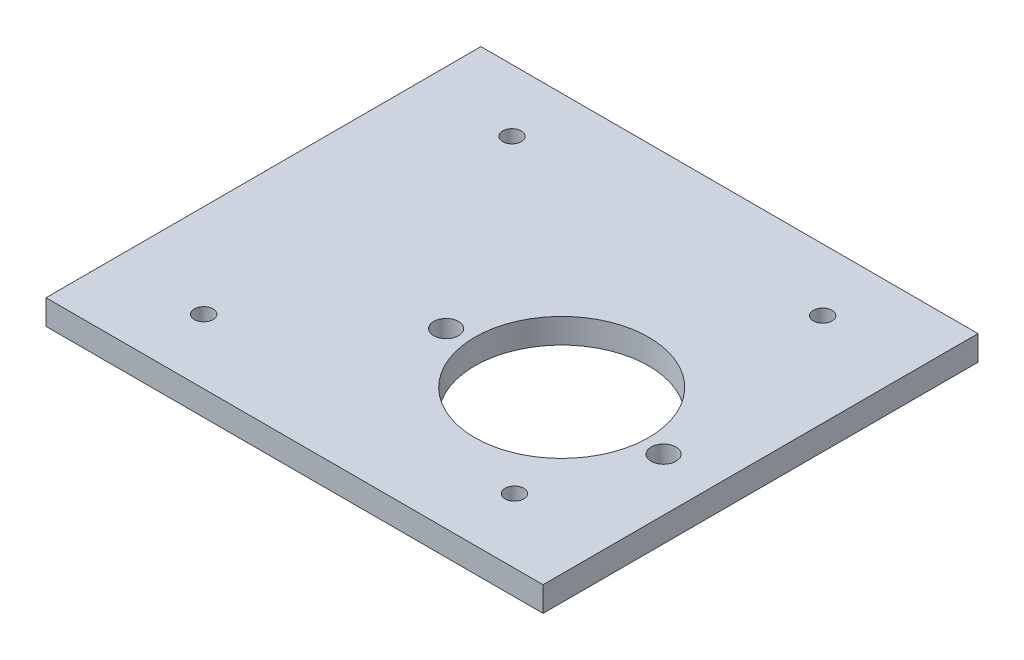
SolidWorks part; units mm, degrees
ref_plane "Front Plane" through (0, 0, 0) normal (0, 0, 1) x (1, 0, 0)
ref_plane "Top Plane" through (0, 0, 0) normal (0, 1, 0) x (1, 0, 0)
ref_plane "Right Plane" through (0, 0, 0) normal (1, 0, 0) x (0, 0, -1)
sketch "Sketch1" plane through (0, 0, 0) normal (0, 1, 0) x (1, 0, 0)
  line L0 (0, 8.2993) -> (0, -7.906) construction
  line L1 (-40, 35) -> (40, 35)
  line L2 (-40, 35) -> (-40, -35)
  line L3 (-40, -35) -> (40, -35)
  line L4 (40, 35) -> (40, -35)
  line L5 (-40, 35) -> (40, -35) construction
  line L6 (-40, -35) -> (40, 35) construction
  line L7 (-14.9915, 0.1967) -> (11.9413, 0.1967) construction
  line L9 (35.0085, 0.1967) -> (61.9413, 0.1967) construction
  line L11 (12.45, 3.05) -> (12.45, -0.95)
  line L13 (15.4498, 2.824) -> (15.4498, -0.9175)
  line L14 (12.45, 3.05) -> (15.4498, -0.9175) construction
  line L15 (12.45, -0.95) -> (15.4498, 2.824) construction
  circle A0 centre (-25, 25) radius 1.5
  circle A1 centre (25, 25) radius 1.5
  circle A2 centre (25, -24.6067) radius 1.5
  circle A3 centre (-25, -24.6067) radius 1.5
  circle A4 centre (14, 1) radius 10
  circle A5 centre (-16, 1) radius 20
  arc A6 (12.45, 3.05) -> (15.4498, 2.824) centre (13.7999, 0.9458) cw
  arc A7 (12.45, -0.95) -> (15.4498, -0.9175) centre (13.9283, 1.0661) ccw
  circle A8 centre (13.9283, 1.0661) radius 4.5
  circle A9 centre (14, -6) radius 14
  circle A10 centre (-3.5, -7.1027) radius 2
  circle A11 centre (31.5, -7.1027) radius 2
  point P0 (0, 0)
  dimension "D3" = 15
  dimension "D6" = 3
  dimension "D7" = 26
  dimension "D10" = 20
  dimension "D11" = 9
  dimension "D12" = 7
  dimension "D13" = 17.5
  dimension "D14" = 4
  dimension "D15" = 4
  dimension "D17" = 40
  dimension "D1" = 80
  dimension "D2" = 70
  dimension "D4" = 10
  dimension "D8" = 4
  dimension "D9" = 3
  dimension "D16" = 17.5
  dimension "D18" = 36
  dimension "D5" = 2
extrude "Boss-Extrude4" add sketch "Sketch1" along normal blind 4 contours L4 L1 L2 L3 A11 A9 A4 A5 A2 A1 A0 A3 | A9 A5 A10 | A9 A4 region at (0, 0, -33.937) region at (14, 0, -8.4705) region at (-16.5796, 0, -1.1889)
